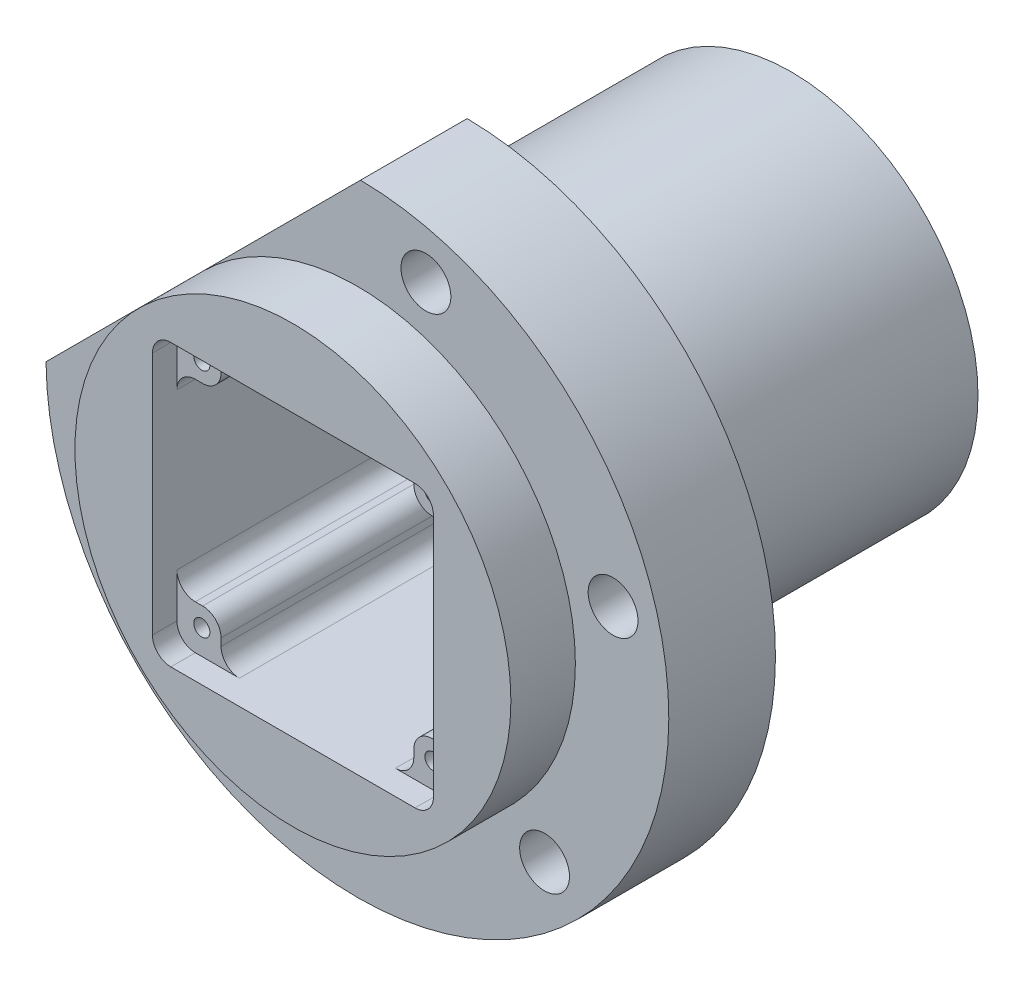
SolidWorks part; units mm, degrees
ref_plane "Front Plane" through (0, 0, 0) normal (0, 0, 1) x (1, 0, 0)
ref_plane "Top Plane" through (0, 0, 0) normal (0, 1, 0) x (1, 0, 0)
ref_plane "Right Plane" through (0, 0, 0) normal (1, 0, 0) x (0, 0, -1)
sketch "Sketch1" plane through (0, 0, 0) normal (0, 0, 1) x (1, 0, 0)
  circle A0 centre (0, 0) radius 44.45
  circle A1 centre (0, 0) radius 63.5
  dimension "D1" = 88.9
  dimension "D2" = 127
extrude "Boss-Extrude1" add sketch "Sketch1" along normal blind 6.35 contours A1 A0 | A0 region at (-61.7039, 0, 0)
extrude "Boss-Extrude2" add sketch "Sketch1<3>" against normal blind 101.6 from offset 19.5 contours A0 region at (0, 0, 0)
sketch "Sketch1<3>" plane through (0, 0, 0) normal (0, 0, 1) x (1, 0, 0) same geometry as "Sketch1"
sketch "Sketch2" plane through (0, 0, 19.5) normal (0, 0, -1) x (-1, 0, 0)
  line L0 (-19.65, 28.65) -> (-19.65, 19.65)
  line L1 (-28.65, -28.65) -> (28.65, -28.65) construction
  line L2 (-28.65, -28.65) -> (-28.65, 28.65) construction
  line L3 (-28.65, 28.65) -> (28.65, 28.65) construction
  line L4 (28.65, -28.65) -> (28.65, 28.65) construction
  line L5 (-28.65, -28.65) -> (28.65, 28.65) construction
  line L6 (-28.65, 28.65) -> (28.65, -28.65) construction
  line L7 (-19.65, 19.65) -> (-28.65, 19.65)
  line L8 (-28.65, 19.65) -> (-28.65, -19.65)
  line L9 (-28.65, -19.65) -> (-19.65, -19.65)
  line L10 (-19.65, -19.65) -> (-19.65, -28.65)
  line L11 (-19.65, -28.65) -> (19.65, -28.65)
  line L12 (19.65, -28.65) -> (19.65, -19.65)
  line L13 (19.65, -19.65) -> (28.65, -19.65)
  line L14 (28.65, -19.65) -> (28.65, 19.65)
  line L15 (28.65, 19.65) -> (19.65, 19.65)
  line L16 (19.65, 19.65) -> (19.65, 28.65)
  line L17 (19.65, 28.65) -> (-19.65, 28.65)
  point P0 (0, 0)
  dimension "D1" = 57.3
  dimension "D2" = 9
extrude "Cut-Extrude1" cut sketch "Sketch2" along normal through all
fillet "Fillet1" radius 3.75 12 edges at (19.65, -19.65, -31.3) (-19.65, -19.65, -31.3) (-19.65, 19.65, -31.3) (19.65, 19.65, -31.3) (-28.65, 19.65, -31.3) (-19.65, -28.65, -31.3) (19.65, -28.65, -31.3) (28.65, -19.65, -31.3) (28.65, 19.65, -31.3) (19.65, 28.65, -31.3) (-19.65, 28.65, -31.3) (-28.65, -19.65, -31.3)
sketch "Sketch3" plane through (0, 0, 19.5) normal (0, 0, -1) x (-1, 0, 0)
  line L1 (-24.9, -28.65) -> (24.9, -28.65)
  line L2 (-28.65, -24.9) -> (-28.65, 24.9)
  line L3 (-24.9, 28.65) -> (24.9, 28.65)
  line L4 (28.65, -24.9) -> (28.65, 24.9)
  line L5 (-28.65, -28.65) -> (28.65, 28.65) construction
  line L6 (-28.65, 28.65) -> (28.65, -28.65) construction
  arc A0 (-24.9, -28.65) -> (-28.65, -24.9) centre (-24.9, -24.9) cw
  arc A1 (24.9, -28.65) -> (28.65, -24.9) centre (24.9, -24.9) ccw
  arc A2 (24.9, 28.65) -> (28.65, 24.9) centre (24.9, 24.9) cw
  arc A3 (-28.65, 24.9) -> (-24.9, 28.65) centre (-24.9, 24.9) cw
  point P0 (0, 0)
  dimension "D2" = 3.75
  dimension "D1" = 57.3
extrude "Cut-Extrude2" cut sketch "Sketch3" along normal blind 5
sketch "Sketch4" plane through (0, 0, 0) normal (0, 0, -1) x (-1, 0, 0)
  circle A0 centre (0, 0) radius 44.45 construction
  circle A1 centre (0, 0) radius 63.5
  circle A2 centre (0, 0) radius 63.5
  circle A3 centre (0, 0) radius 44.45
  dimension "D1" = 0
extrude "Boss-Extrude3" add sketch "Sketch4" along normal blind 15.4
ref_plane "Plane1" through (0, 0, -7.4) normal (0, 0, -1) x (-1, 0, 0)
hole_wizard "CSK for #8 Flat Head Machine Screw1" positions "Sketch6" profile "Sketch7" countersink size "#8" standard "ANSI Inch" end condition through all
sketch "Sketch6" plane through (0, 0, -7.4) normal (0, 0, 1) x (1, 0, 0)
  line L0 (0, 0) -> (38.1661, -38.1661) construction
  line L2 (-24.9, 28.65) -> (24.9, 28.65) construction
  line L3 (31.4309, -31.4309) -> (44.9013, -44.9013) construction
  line L4 (0, 0) -> (38.1661, -38.1661) construction
  circle A0 centre (0, 0) radius 44.45 construction
  circle A1 centre (0, 0) radius 44.45 construction
  circle A4 centre (0, 0) radius 44.45 construction
  circle A5 centre (0, 0) radius 63.5
  circle A6 centre (0, 0) radius 63.5 construction
  point P0 (38.1661, -38.1661)
  point P45 (-13.9698, -52.1358)
  point P46 (-52.1358, -13.9698)
  point P47 (-38.1661, 38.1661)
  point P48 (13.9698, 52.1358)
  point P49 (52.1358, 13.9698)
  dimension "D1" = 45
  dimension "D2" = 6
sketch "Sketch7" plane through (38.1661, -38.1661, -7.4) normal (1, 0, 0) x (0, -1, 0)
  line L0 (0, 0) -> (0, 74.7)
  line L1 (0, 74.7) -> (2.2479, 74.7)
  line L2 (2.2479, 74.7) -> (2.2479, 3.2645)
  line L3 (2.2479, 3.2645) -> (5.0857, 0)
  line L5 (5.0857, 0) -> (0, 0)
  line L6 (-2.2479, 3.2645) -> (-5.0857, 0) construction
  line L11 (0, -6.35) -> (0, 107.95) construction
  dimension "Thru Hole Dia." = 4.4958
  dimension "Thru Hole Depth" = 74.7
  dimension "Near C'Sink Dia." = 10.1714
  dimension "Near C'Sink Angle" = 82
sketch "Sketch5" plane through (0, 0, 6.35) normal (0, 0, 1) x (1, 0, 0)
  line L0 (0.635, 63.4968) -> (-63.4968, -0.635)
  line L1 (-24.9, 28.65) -> (24.9, 28.65) construction
  circle A0 centre (0, 0) radius 63.5 construction
  circle A1 centre (0, 0) radius 44.45 construction
  circle A2 centre (0, 0) radius 63.5
  circle M3 centre (0, 0) radius 63.5
  dimension "D1" = 45
extrude "Cut-Extrude3" cut sketch "Sketch5" against normal through all contours L0 M3 region at (-36.895, 36.895, 6.35)
sketch "Sketch8" plane through (0, 0, -7.4) normal (0, 0, -1) x (-1, 0, 0)
  circle A4 centre (-38.1661, -38.1661) radius 5.0857 construction
  circle A9 centre (-38.1661, -38.1661) radius 5.0857
  circle A10 centre (52.1358, -13.9698) radius 5.0857 construction
  circle A11 centre (13.9698, -52.1358) radius 5.0857 construction
  circle A12 centre (-52.1358, 13.9698) radius 5.0857 construction
  circle A13 centre (-13.9698, 52.1358) radius 5.0857 construction
  circle A14 centre (52.1358, -13.9698) radius 5.0857
  circle A15 centre (13.9698, -52.1358) radius 5.0857
  circle A16 centre (-52.1358, 13.9698) radius 5.0857
  circle A17 centre (-13.9698, 52.1358) radius 5.0857
extrude "Cut-Extrude4" cut sketch "Sketch8" against normal through all
hole_wizard "Tap Drill for M4x0.7 Tap1" positions "Sketch10" profile "Sketch11" hole size "M4x0.7" standard "ANSI Metric" end condition through all
sketch "Sketch10" plane through (0, 0, 14.5) normal (0, 0, 1) x (1, 0, 0)
  point P0 (-23.57, 23.57)
  point P2 (23.57, 23.57)
  point P4 (23.57, -23.57)
  point P6 (-23.57, -23.57)
  dimension "D1" = 47.14
  dimension "D2" = 47.14
  dimension "D3" = 23.57
  dimension "D4" = 23.57
sketch "Sketch11" plane through (-23.57, 23.57, 14.5) normal (1, 0, 0) x (0, -1, 0)
  line L0 (0, 0) -> (0, 96.6)
  line L1 (0, 96.6) -> (1.65, 96.6)
  line L2 (1.65, 96.6) -> (1.65, 0)
  line L5 (1.65, 0) -> (0, 0)
  line L11 (0, -6.35) -> (0, 107.95) construction
  dimension "Thru Hole Dia." = 3.3
  dimension "Thru Hole Depth" = 96.6
sketch "Sketch12" plane through (0, 0, -82.1) normal (0, 0, -1) x (-1, 0, 0)
  circle A0 centre (0, 0) radius 38.1
  circle A1 centre (0, 0) radius 44.45 construction
  circle A2 centre (0, 0) radius 44.45
  dimension "D1" = 76.2
extrude "Cut-Extrude5" cut sketch "Sketch12" against normal up to surface (66.7 mm away) up to face at (49.8879, 13.9698, -15.4)
